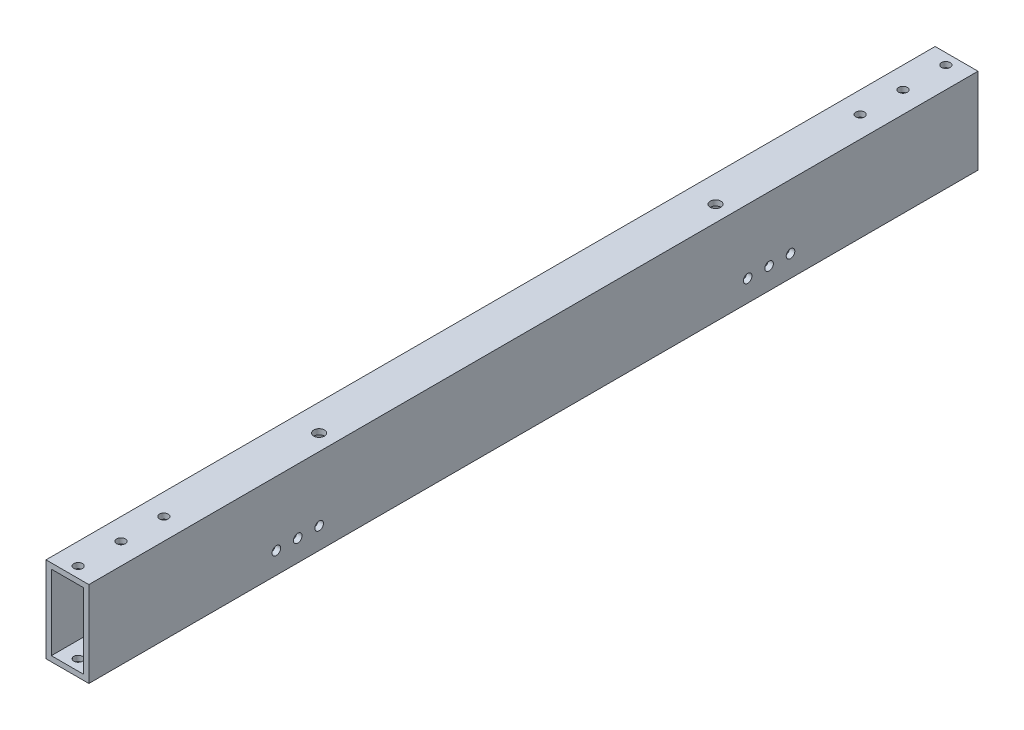
SolidWorks part; units mm, degrees
material "6061-T6 (SS)"
ref_plane "Front" through (0, 0, 0) normal (0, 0, 1) x (1, 0, 0)
ref_plane "Top" through (0, 0, 0) normal (0, 1, 0) x (1, 0, 0)
ref_plane "Right" through (0, 0, 0) normal (1, 0, 0) x (0, 0, -1)
sketch "Sketch1" plane through (0, 0, 0) normal (0, 0, 1) x (1, 0, 0)
  line L1 (-12.7, -25.4) -> (12.7, -25.4)
  line L2 (-12.7, -25.4) -> (-12.7, 25.4)
  line L3 (-12.7, 25.4) -> (12.7, 25.4)
  line L4 (12.7, -25.4) -> (12.7, 25.4)
  line L5 (-12.7, -25.4) -> (12.7, 25.4) construction
  line L6 (-12.7, 25.4) -> (12.7, -25.4) construction
  point P0 (0, 0)
  dimension "D1" = 25.4
  dimension "D2" = 50.8
extrude "Extrude-Thin1" add sketch "Sketch1" along normal blind 527.05 thin thin type one direction reverse wall 3.175
hole_wizard "#10 Clearance Hole1" positions "Sketch2" profile "Sketch3" hole size "#10" standard "ANSI Inch" end condition through all
sketch "Sketch2" plane through (0, 25.4, 0) normal (0, 1, 0) x (1, 0, 0)
  line L0 (12.7, -527.05) -> (-12.7, -527.05) construction
  line L1 (-12.7, -527.05) -> (-12.7, 0) construction
  point P0 (0, -520.7)
  point P2 (0, -495.3)
  point P4 (0, -469.9)
  point P6 (0, -6.35)
  point P8 (0, -31.75)
  point P10 (0, -57.15)
  dimension "D1" = 6.35
  dimension "D2" = 12.7
  dimension "D3" = 25.4
  dimension "D4" = 25.4
  dimension "D5" = 6.35
  dimension "D6" = 25.4
  dimension "D7" = 25.4
sketch "Sketch3" plane through (0, 25.4, 520.7) normal (1, 0, 0) x (0, 0, 1)
  line L0 (0, 0) -> (0, 50.8)
  line L1 (0, 50.8) -> (2.5527, 50.8)
  line L2 (2.5527, 50.8) -> (2.5527, 0)
  line L5 (2.5527, 0) -> (0, 0)
  line L11 (0, -6.35) -> (0, 107.95) construction
  dimension "Thru Hole Dia." = 5.1054
  dimension "Thru Hole Depth" = 50.8
sketch "Sketch6" plane through (0, -25.4, 0) normal (0, -1, 0) x (-1, 0, 0)
  point P0 (3.175, -70.358)
  point P3 (-3.175, -95.758)
  point P6 (3.175, -121.158)
  point P9 (-3.175, -146.558)
  point P12 (3.175, -171.958)
  point P15 (-3.175, -197.358)
  point P22 (-3.175, -248.158)
  point P25 (3.175, -273.558)
  point P28 (-3.175, -298.958)
  point P31 (3.175, -324.358)
  point P34 (-3.175, -349.758)
  point P37 (3.175, -375.158)
  point P40 (-3.175, -400.558)
  point P43 (3.175, -425.958)
  point P46 (-3.175, -451.358)
  point P54 (3.175, -222.758)
hole_wizard "1/8 (0.13) Diameter Hole1" positions "Sketch6" profile "Sketch5" hole size "1/8" standard "ANSI Inch" end condition up to next
sketch "Sketch5" plane through (-3.175, -25.4, 70.358) normal (1, 0, 0) x (0, 0, -1)
  line L0 (0, 0) -> (0, 3.175)
  line L1 (0, 3.175) -> (1.651, 3.175)
  line L2 (1.651, 3.175) -> (1.651, 0)
  line L5 (1.651, 0) -> (0, 0)
  line L11 (0, -6.35) -> (0, 107.95) construction
  dimension "Thru Hole Dia." = 3.302
  dimension "Thru Hole Depth" = 3.175
sketch "Sketch9" plane through (0, 25.4, 0) normal (0, 1, 0) x (1, 0, 0)
  line L0 (12.7, 0) -> (-12.7, 0) construction
  line L1 (12.7, -527.05) -> (12.7, 0) construction
  line L2 (12.7, -527.05) -> (-12.7, -527.05) construction
  point P0 (3.175, -146.05)
  point P2 (3.175, -381)
  dimension "D1" = 146.05
  dimension "D2" = 9.525
  dimension "D3" = 146.05
hole_wizard "1/4 (0.25) Diameter Hole1" positions "Sketch9" profile "Sketch8" hole size "1/4" standard "ANSI Inch"
sketch "Sketch8" plane through (3.175, 25.4, 146.05) normal (1, 0, 0) x (0, 0, 1)
  line L0 (0, 0) -> (0, 12.6265)
  line L1 (0, 12.6265) -> (3.175, 10.7188)
  line L2 (3.175, 10.7188) -> (3.175, 0)
  line L5 (3.175, 0) -> (0, 0)
  line L10 (0, 12.6265) -> (-3.175, 10.7188) construction
  line L11 (0, -6.35) -> (0, 107.95) construction
  dimension "Hole Dia." = 6.35
  dimension "Hole Depth" = 10.7188
  dimension "Drill Angle" = 118
sketch "Sketch12" plane through (-12.7, 0, 0) normal (-1, 0, 0) x (0, 0, 1)
  point P44 (111.125, -12.7)
  point P47 (123.825, -12.7)
  point P50 (136.525, -12.7)
  point P53 (390.525, -12.7)
  point P56 (403.225, -12.7)
  point P59 (415.925, -12.7)
hole_wizard "CBORE for #10 Socket Head Cap Screw1" positions "Sketch12" profile "Sketch11" counterbore size "#10" standard "ANSI Inch" end condition through all
sketch "Sketch11" plane through (-12.7, -12.7, 111.125) normal (0, 1, 0) x (0, 0, 1)
  line L0 (0, 0) -> (0, 25.4)
  line L1 (0, 25.4) -> (2.5527, 25.4)
  line L3 (2.5527, 25.4) -> (2.5527, 8.001)
  line L4 (2.5527, 8.001) -> (4.7625, 8.001)
  line L5 (4.7625, 8.001) -> (4.7625, 0)
  line L7 (4.7625, 0) -> (0, 0)
  line L11 (0, -6.35) -> (0, 107.95) construction
  dimension "Thru Hole Dia." = 5.1054
  dimension "Thru Hole Depth" = 25.4
  dimension "C'Bore Dia." = 9.525
  dimension "C'Bore Depth" = 8.001
